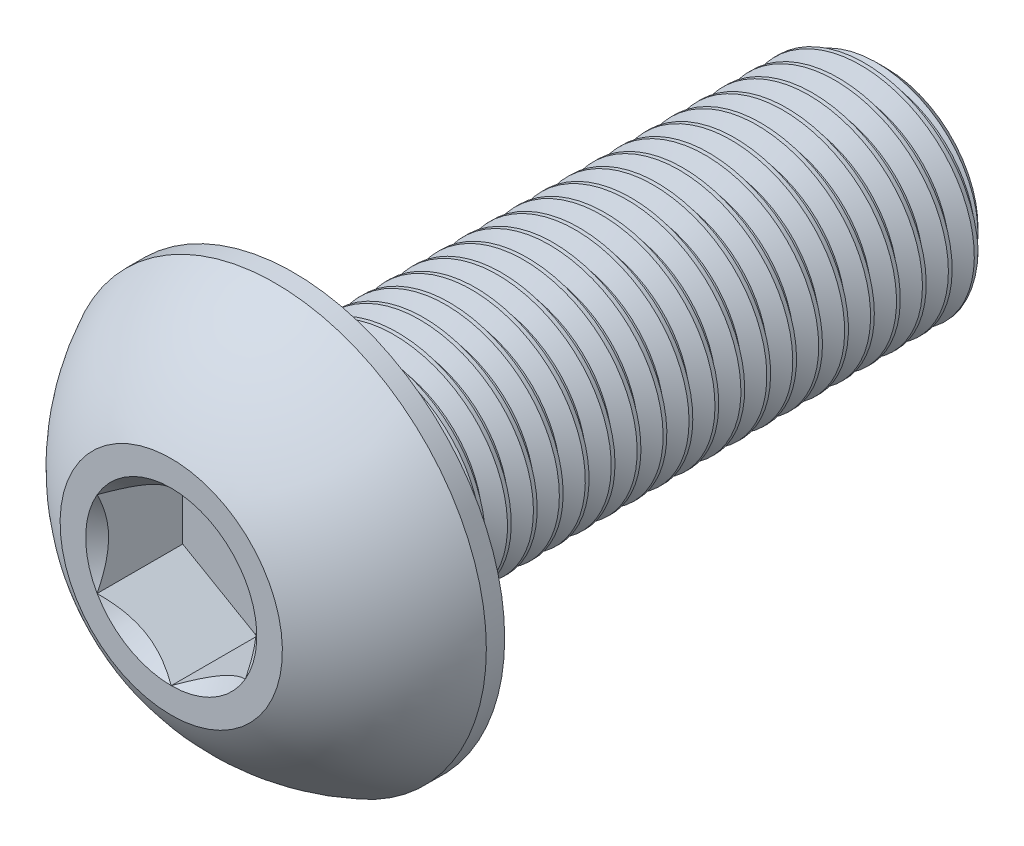
SolidWorks part; units mm, degrees
ref_plane "Front" through (0, 0, 0) normal (0, 0, 1) x (1, 0, 0)
ref_plane "Top" through (0, 0, 0) normal (0, 1, 0) x (1, 0, 0)
ref_plane "Right" through (0, 0, 0) normal (1, 0, 0) x (0, 0, -1)
sketch "Sketch1" plane through (0, 0, 0) normal (1, 0, 0) x (0, 0, -1)
  line L2 (1.65, 1.5) -> (9.65, 1.5)
  line L3 (9.65, 1.5) -> (9.65, 0)
  line L4 (9.65, 0) -> (1.65, 0)
  line L6 (1.4025, 2.85) -> (1.65, 2.85) construction
  line L7 (9.65, 1.5) -> (9.65, -1.5) construction
  line L8 (0, 0) -> (1.65, 0) construction
  line L9 (1.65, 2.85) -> (1.65, -2.85) construction
  line L11 (1.65, 1.5) -> (1.65, 0)
  line L13 (0, 1) -> (0, -1) construction
  line L14 (0, 1) -> (0, 1.5) construction
  arc A3 (0, 1.5) -> (1.4025, 2.85) centre (2.7948, 0) cw construction
  dimension "D1" = 0.2475
  dimension "Head Ht" = 1.65
  dimension "Head Dia" = 5.7
  dimension "Dia" = 3
  dimension "Lg" = 8
  dimension "Hex" = 2
revolve "Revolve1" add sketch "Sketch1" angle 360 mid plane about L4
sketch "Sketch3" plane through (0, 0, -9.65) normal (0, 0, -1) x (-1, 0, 0)
  circle A0 centre (0, 0) radius 1.5
curve "Helix/Spiral1" pitch 0.35 height 8.35 radius 1.5 centre (0, 0, -9.65) axis (0, 0, 1) start towards (0, 1, 0)
sketch "Sketch2" plane through (0, 0, 0) normal (1, 0, 0) x (0, 0, -1)
  line L0 (9.65, 1.5) -> (9.9492, 1.5)
  line L1 (9.9492, 1.5) -> (9.825, 1.2848)
  line L2 (9.825, 1.2848) -> (9.7743, 1.2848)
  line L3 (9.7743, 1.2848) -> (9.65, 1.5)
  line L4 (9.7121, 1.3924) -> (9.8871, 1.3924) construction
  point P9 (10.3886, -0.7655)
  dimension "D1" = 60
  dimension "D2" = 0.0508
  dimension "D3" = 0.175
chamfer "Chamfer1" distance 0.2625 angle 45 1 edges at (0, 1.5, -9.65)
sweep "Cut-Sweep1" cut profiles "Sketch2" path "Helix/Spiral1"
sketch "Sketch7" plane through (0, 0, 0) normal (1, 0, 0) x (0, 0, -1)
  line L6 (1.4025, 2.85) -> (1.65, 2.85) construction
  line L8 (0, 0) -> (1.65, 0) construction
  line L11 (1.65, 2.85) -> (1.65, -2.85) construction
  line L12 (1.4025, 2.85) -> (1.65, 2.85)
  line L13 (0, 0) -> (1.65, 0)
  line L14 (0, 1) -> (0, -1) construction
  line L15 (1.65, 2.85) -> (1.65, 0)
  line L16 (0, 1.5) -> (0, 0)
  arc A2 (1.4025, 2.85) -> (0, 1.5) centre (2.7948, 0) ccw construction
  arc A3 (1.4025, 2.85) -> (0, 1.5) centre (2.7948, 0) ccw
revolve "Revolve2" add sketch "Sketch7" angle 360 mid plane about L13
sketch "Sketch5" plane through (0, 0, 0) normal (0, 0, 1) x (1, 0, 0)
  line L1 (1, -0.5774) -> (1, 0.5774)
  line L2 (1, 0.5774) -> (0, 1.1547)
  line L3 (0, 1.1547) -> (-1, 0.5774)
  line L4 (-1, 0.5774) -> (-1, -0.5774)
  line L5 (-1, -0.5774) -> (0, -1.1547)
  line L6 (0, -1.1547) -> (1, -0.5774)
  circle A0 centre (0, 0) radius 1 construction
extrude "Cut-Extrude2" cut sketch "Sketch5" against normal blind 1.155
sketch "Sketch6" plane through (0, 0, 0) normal (0, 0, 1) x (1, 0, 0)
  circle A0 centre (0, 0) radius 1.1547
extrude "Cut-Extrude3" cut sketch "Sketch6" against normal blind 1.155 draft 45
sketch "Sketch9" [suppressed] plane through (0, 0, -6.6) normal (0, 0, 1) x (1, 0, 0)
  circle A2 centre (0, 0) radius 6
extrude "Boss-Extrude2" [suppressed] add sketch "Sketch9" against normal offset from surface (19 mm away) 32 up to face at (0, 1.2375, -9.65)
sketch "Sketch10" plane through (0, 0, 0) normal (1, 0, 0) x (0, 0, -1)
  line L0 (9.65, 1.5) -> (9.65, -1.5) construction
  point P0 (9.125, -1.5)
  dimension "D1" = 0.525
equation "\"D3@Helix/Spiral1\" = \"Lg@Sketch1\" + \"D4@Helix/Spiral1\""
equation "\"D2@Sketch2\"=\"D4@Helix/Spiral1\" * .145"
equation "\"D3@Sketch2\" = \"D4@Helix/Spiral1\" * .5"
equation "\"D1@Chamfer1\" = \"D4@Helix/Spiral1\" * .75"
equation "\"D1@Cut-Extrude2\" = \"Head Ht@Sketch1\" * .7"
equation "\"D1@Sketch1\" = \"Head Ht@Sketch1\" * .15"
equation "\"D1@Sketch10\" = \"D4@Helix/Spiral1\" * 1.5"
equation "\"D1@Cut-Extrude3\" = \"D1@Cut-Extrude2\""
